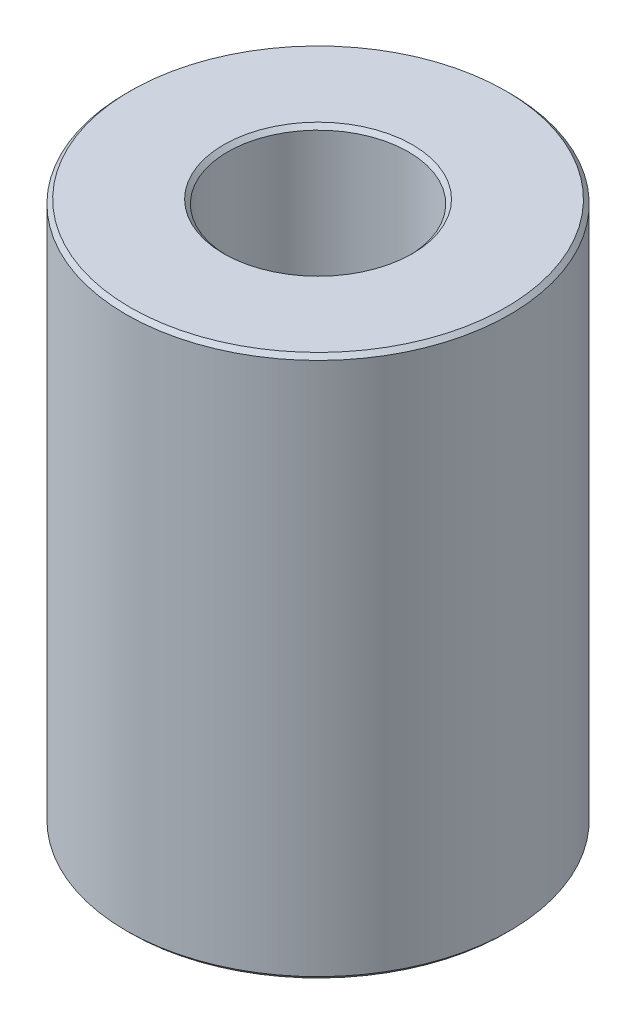
SolidWorks part; units mm, degrees
ref_plane "Front Plane" through (0, 0, 0) normal (0, 0, 1) x (1, 0, 0)
ref_plane "Top Plane" through (0, 0, 0) normal (0, 1, 0) x (1, 0, 0)
ref_plane "Right Plane" through (0, 0, 0) normal (1, 0, 0) x (0, 0, -1)
sketch "Sketch1" plane through (0, 0, 0) normal (0, 1, 0) x (1, 0, 0)
  circle A0 centre (0, 0) radius 12.5
  dimension "SLEEVE_OD" = 25
extrude "Boss-Extrude1" add sketch "Sketch1" along normal blind 35.3197
sketch "Sketch2" plane through (0, 0, 0) normal (0, 1, 0) x (1, 0, 0)
  circle A0 centre (0, 0) radius 5.8879
  dimension "BORE_D" = 11.7758
extrude "Cut-Extrude1" cut sketch "Sketch2" along normal through all
chamfer "Chamfer1" distance 0.2653 angle 45 4 edges at (0, 35.3197, 5.8879) (0, 0, 5.8879) (0, 0, 12.5) (0, 35.3197, 12.5)
